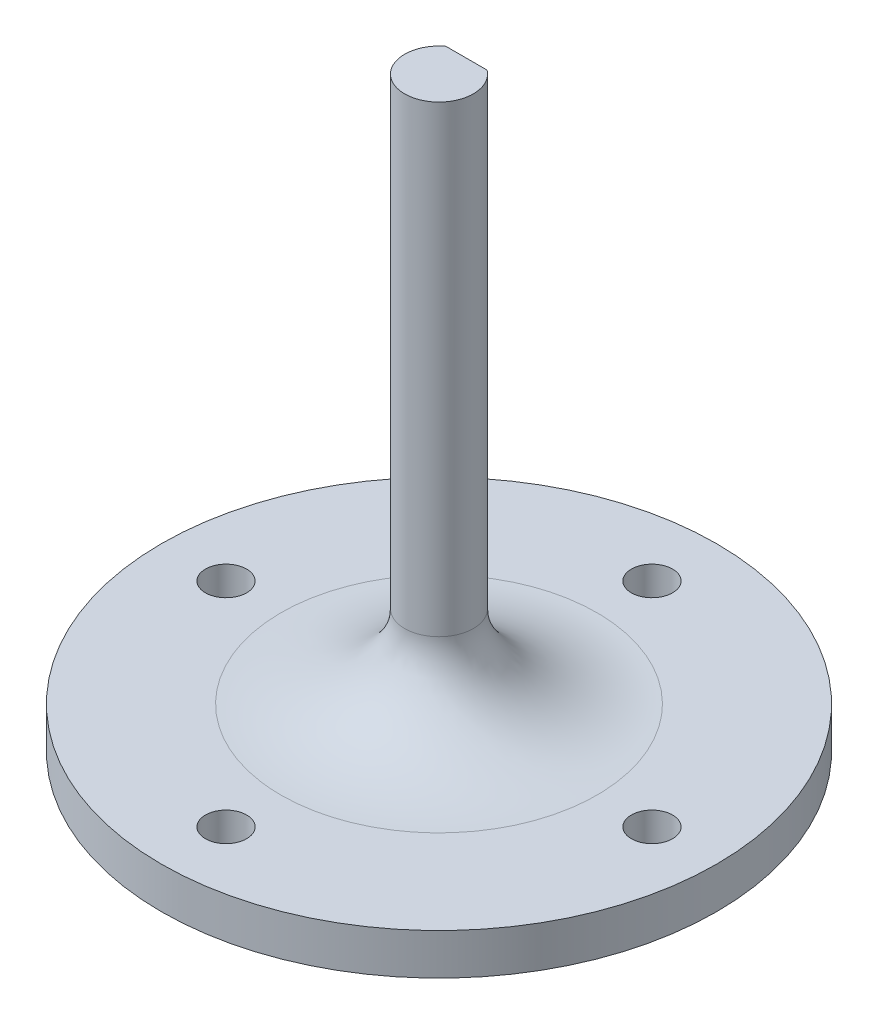
SolidWorks part; units mm, degrees
ref_plane "Front Plane" through (0, 0, 0) normal (0, 0, 1) x (1, 0, 0)
ref_plane "Top Plane" through (0, 0, 0) normal (0, 1, 0) x (1, 0, 0)
ref_plane "Right Plane" through (0, 0, 0) normal (1, 0, 0) x (0, 0, -1)
sketch "Sketch2" plane through (0, 0, 0) normal (0, 1, 0) x (1, 0, 0)
  line L0 (-1.5, 2) -> (1.5, 2)
  circle A0 centre (0, 0) radius 15.5 construction
  circle A1 centre (0, 15.5) radius 1.5
  circle A2 centre (-15.5, 0) radius 1.5
  circle A3 centre (0, -15.5) radius 1.5
  circle A4 centre (15.5, 0) radius 1.5
  circle A5 centre (0, 0) radius 2.5
  circle A6 centre (0, 0) radius 20.2034
  dimension "D2" = 3
  dimension "D3" = 5
  dimension "D1" = 15.5
  dimension "D4" = 2
extrude "Boss-Extrude1" add sketch "Sketch2" against normal blind 3 contours A6 A1 A2 A3 A4 A5 | L0 A5 | L0 A5 region at (0, 0, -2.2018) region at (0, 0, 0.1209) region at (-19.632, 0, 0)
extrude "Boss-Extrude2" add sketch "Sketch2<3>" along normal blind 39.7 contours L0 A5 region at (0, 0, 0.1209)
sketch "Sketch2<3>" plane through (0, 0, 0) normal (0, 1, 0) x (1, 0, 0) same geometry as "Sketch2"
extrude "Boss-Extrude3" add sketch "Sketch2<4>" along normal blind 6 contours L0 A5 region at (0, 0, -2.2018)
sketch "Sketch2<4>" plane through (0, 0, 0) normal (0, 1, 0) x (1, 0, 0) same geometry as "Sketch2"
chamfer "Chamfer1" [suppressed] distance 9 distance2 6
fillet "Fillet1" radius 9 1 edges at (0, 0, 2.5) second distance 6 first distance on face at (0, 0, 20.2034)
fillet "Fillet2" radius 0.5 1 edges
equation "\"largeBearOD\"= 21mm"
equation "\"largeBearID\" = 15mm"
equation "\"largeBearOTight\"= 0.34375mm'calibrate - hold onto gears"
equation "\"largeBearITight\"= 0mm'calibrate - hold onto eccentric nut"
equation "\"largeBearFlangeDiam\" = 22.5mm"
equation "\"largeBearFlangeWidth\" = 0.8mm"
equation "\"smallBearOD\"= 14.8mm"
equation "\"smallBearOTight\"= 0mm'calibrate - hold onto bottom of gearbox"
equation "\"smallBearOLoose\"= 0mm'calibrate - able to take off topHat"
equation "\"smallBearID\" = 10mm"
equation "\"smallBearITight\" = 0mm'hold onto "
equation "\"pinCircleDiam\"= 75mm"
equation "\"pinDiam\"= 6mm"
equation "\"sheetThickness\"= 0.1875in"
equation "\"ballBearDiam\"= 3.5mm"
equation "\"thrustBearingThickness\"= 5mm'measure this irl and change"
equation "\"thrustBearingID\"= 0mm'measure this irl and change"
equation "\"thrustBearingOD\"= 0mm'measure this irl and change"
equation "\"eccentricity\" = 1mm"
equation "\"dShaftDiam\"= 5mm"
